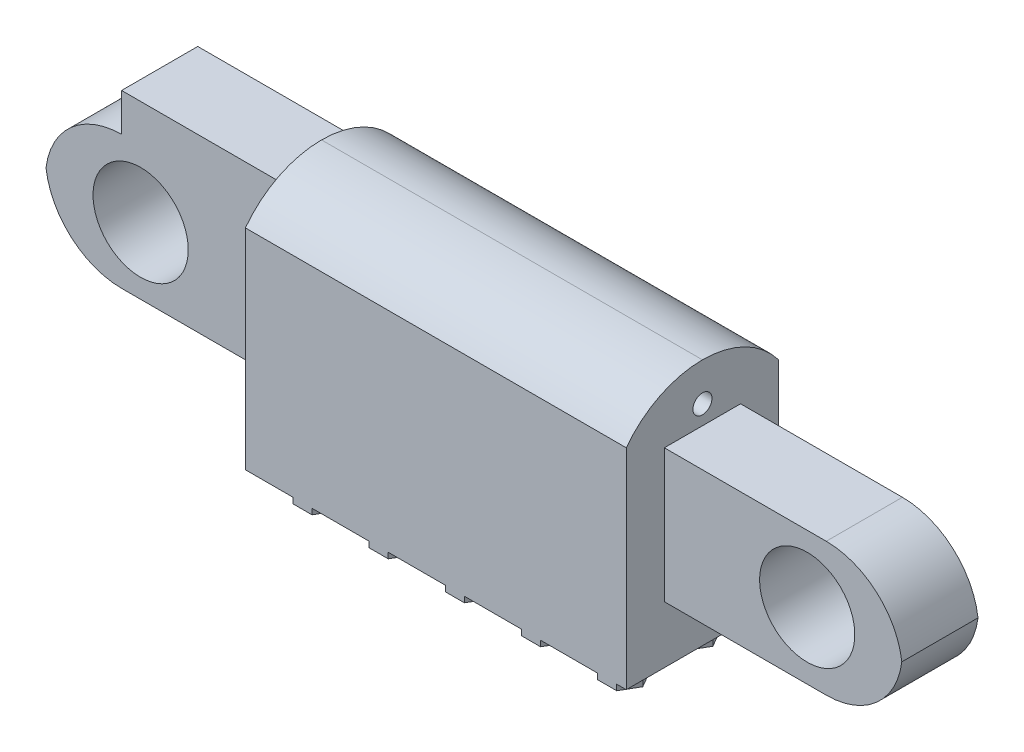
SolidWorks part; units mm, degrees
material "PLA"
ref_plane "Front" through (0, 0, 0) normal (0, 0, 1) x (1, 0, 0)
ref_plane "Top" through (0, 0, 0) normal (0, 1, 0) x (1, 0, 0)
ref_plane "Right" through (0, 0, 0) normal (1, 0, 0) x (0, 0, -1)
sketch "Sketch1" plane through (0, 0, 0) normal (0, 0, 1) x (1, 0, 0)
  line L1 (-6.35, 4.445) -> (9.525, 4.445)
  line L2 (-6.35, 4.445) -> (-6.35, -4.445)
  line L3 (-6.35, -4.445) -> (9.525, -4.445)
  line L4 (9.525, 4.445) -> (9.525, -4.445)
  circle A0 centre (0, 0) radius 3.175
  dimension "D1" = 6.35
  dimension "D2" = 6.35
  dimension "D3" = 4.445
  dimension "D4" = 4.445
  dimension "D5" = 15.875
extrude "Boss-Extrude1" add sketch "Sketch1" along normal blind 5.08
fillet "Fillet1" radius 5.08 2 edges at (-6.35, -4.445, 2.54) (-6.35, 4.445, 2.54)
sketch "Sketch2" plane through (9.525, 0, 0) normal (1, 0, 0) x (0, 0, -1)
  line L0 (-8.89, -8.255) -> (3.81, -8.255)
  line L1 (3.81, -8.255) -> (3.81, 8.255)
  line L2 (3.81, 8.255) -> (-8.89, 8.255)
  line L3 (-8.89, 8.255) -> (-8.89, -8.255)
  line L4 (0, -4.445) -> (0, 4.445)
  line L5 (0, 4.445) -> (-5.08, 4.445)
  line L6 (-5.08, 4.445) -> (-5.08, -4.445)
  line L7 (-5.08, -4.445) -> (0, -4.445)
  line L8 (0, -4.445) -> (0, 4.445)
  line L9 (0, 4.445) -> (-5.08, 4.445)
  line L10 (-5.08, 4.445) -> (-5.08, -4.445)
  line L11 (-5.08, -4.445) -> (0, -4.445)
  line M5 (0, -4.445) -> (0, 4.445)
  line M6 (0, 4.445) -> (-5.08, 4.445)
  line M7 (-5.08, 4.445) -> (-5.08, -4.445)
  line M8 (-5.08, -4.445) -> (0, -4.445)
  dimension "D1" = 0
  dimension "D2" = 3.81
extrude "Boss-Extrude2" add sketch "Sketch2" along normal blind 25.4 separate body contours L2 L3 L0 L1 M5 M8 M7 M6 | M8 M5 M6 M7 region at (9.525, 0, 8.6817) region at (9.525, 0, 2.54)
ref_plane "Plane1" through (22.225, 0, 0) normal (-1, 0, 0) x (0, 0, 1)
mirror "Mirror7" about plane through (22.225, 0, 0) normal (-1, 0, 0) of bodies 101
fillet "Fillet3" radius 6.35 2 edges at (22.225, 8.255, -3.81) (22.225, 8.255, 8.89)
sketch "Sketch3" plane through (0, 4.445, 0) normal (0, 1, 0) x (1, 0, 0)
  line L4 (9.525, 0) -> (-1.27, 0)
  line L5 (-1.27, 0) -> (-1.27, -5.08)
  line L6 (-1.27, -5.08) -> (9.525, -5.08)
  line L7 (9.525, -5.08) -> (9.525, 0)
  line L12 (9.525, 0) -> (-1.27, 0)
  line L13 (-1.27, 0) -> (-1.27, -5.08)
  line L14 (-1.27, -5.08) -> (9.525, -5.08)
  line L15 (9.525, -5.08) -> (9.525, 0)
  dimension "D1" = 0
extrude "Boss-Extrude3" add sketch "Sketch3" along normal blind 2.54
sketch "Sketch4" plane through (-1.27, 0, 0) normal (-1, 0, 0) x (0, 0, 1)
  line L8 (5.08, 6.985) -> (5.08, 4.445) construction
  line L9 (0, 4.445) -> (5.08, 4.445) construction
  circle A0 centre (2.54, 5.715) radius 0.635
  dimension "D1" = 1.27
  dimension "D2" = 1.27
  dimension "D3" = 2.54
extrude "Cut-Extrude1" cut sketch "Sketch4" against normal through all
fillet "Fillet6" radius 1.27 2 edges at (22.225, -8.255, -3.81) (22.225, -8.255, 8.89)
sketch "Sketch5" plane through (0, -8.255, 0) normal (0, -1, 0) x (1, 0, 0)
  line L0 (34.925, 1.905) -> (34.925, 3.175) construction
  line L1 (34.925, 7.62) -> (9.525, 7.62)
  line L2 (34.925, 7.62) -> (34.925, -2.54)
  line L3 (34.925, -2.54) -> (9.525, -2.54)
  line L4 (9.525, 7.62) -> (9.525, -2.54)
  line L5 (33.02, 5.4203) -> (34.29, 5.4203)
  line L6 (34.29, 5.4203) -> (34.925, 6.5201)
  line L7 (34.925, 6.5201) -> (34.29, 7.62)
  line L8 (34.29, 7.62) -> (33.02, 7.62)
  line L9 (33.02, 7.62) -> (32.385, 6.5201)
  line L10 (32.385, 6.5201) -> (33.02, 5.4203)
  line L11 (30.48, 5.4203) -> (31.75, 5.4203)
  line L12 (31.75, 5.4203) -> (32.385, 6.5201)
  line L13 (32.385, 6.5201) -> (31.75, 7.62)
  line L14 (31.75, 7.62) -> (30.48, 7.62)
  line L15 (30.48, 7.62) -> (29.845, 6.5201)
  line L16 (29.845, 6.5201) -> (30.48, 5.4203)
  line L17 (27.94, 5.4203) -> (29.21, 5.4203)
  line L18 (29.21, 5.4203) -> (29.845, 6.5201)
  line L19 (29.845, 6.5201) -> (29.21, 7.62)
  line L20 (29.21, 7.62) -> (27.94, 7.62)
  line L21 (27.94, 7.62) -> (27.305, 6.5201)
  line L22 (27.305, 6.5201) -> (27.94, 5.4203)
  line L23 (25.4, 5.4203) -> (26.67, 5.4203)
  line L24 (26.67, 5.4203) -> (27.305, 6.5201)
  line L25 (27.305, 6.5201) -> (26.67, 7.62)
  line L26 (26.67, 7.62) -> (25.4, 7.62)
  line L27 (25.4, 7.62) -> (24.765, 6.5201)
  line L28 (24.765, 6.5201) -> (25.4, 5.4203)
  line L29 (22.86, 5.4203) -> (24.13, 5.4203)
  line L30 (24.13, 5.4203) -> (24.765, 6.5201)
  line L31 (24.765, 6.5201) -> (24.13, 7.62)
  line L32 (24.13, 7.62) -> (22.86, 7.62)
  line L33 (22.86, 7.62) -> (22.225, 6.5201)
  line L34 (22.225, 6.5201) -> (22.86, 5.4203)
  line L35 (20.32, 5.4203) -> (21.59, 5.4203)
  line L36 (21.59, 5.4203) -> (22.225, 6.5201)
  line L37 (22.225, 6.5201) -> (21.59, 7.62)
  line L38 (21.59, 7.62) -> (20.32, 7.62)
  line L39 (20.32, 7.62) -> (19.685, 6.5201)
  line L40 (19.685, 6.5201) -> (20.32, 5.4203)
  line L41 (17.78, 5.4203) -> (19.05, 5.4203)
  line L42 (19.05, 5.4203) -> (19.685, 6.5201)
  line L43 (19.685, 6.5201) -> (19.05, 7.62)
  line L44 (19.05, 7.62) -> (17.78, 7.62)
  line L45 (17.78, 7.62) -> (17.145, 6.5201)
  line L46 (17.145, 6.5201) -> (17.78, 5.4203)
  line L47 (15.24, 5.4203) -> (16.51, 5.4203)
  line L48 (16.51, 5.4203) -> (17.145, 6.5201)
  line L49 (17.145, 6.5201) -> (16.51, 7.62)
  line L50 (16.51, 7.62) -> (15.24, 7.62)
  line L51 (15.24, 7.62) -> (14.605, 6.5201)
  line L52 (14.605, 6.5201) -> (15.24, 5.4203)
  line L53 (12.7, 5.4203) -> (13.97, 5.4203)
  line L54 (13.97, 5.4203) -> (14.605, 6.5201)
  line L55 (14.605, 6.5201) -> (13.97, 7.62)
  line L56 (13.97, 7.62) -> (12.7, 7.62)
  line L57 (12.7, 7.62) -> (12.065, 6.5201)
  line L58 (12.065, 6.5201) -> (12.7, 5.4203)
  line L59 (10.16, 5.4203) -> (11.43, 5.4203)
  line L60 (11.43, 5.4203) -> (12.065, 6.5201)
  line L61 (12.065, 6.5201) -> (11.43, 7.62)
  line L62 (11.43, 7.62) -> (10.16, 7.62)
  line L63 (10.16, 7.62) -> (9.525, 6.5201)
  line L64 (9.525, 6.5201) -> (10.16, 5.4203)
  line L65 (30.48, 3.0835) -> (31.75, 3.0835)
  line L66 (31.75, 3.0835) -> (32.385, 4.1833)
  line L67 (32.385, 4.1833) -> (31.75, 5.2832)
  line L68 (31.75, 5.2832) -> (30.48, 5.2832)
  line L69 (30.48, 5.2832) -> (29.845, 4.1833)
  line L70 (29.845, 4.1833) -> (30.48, 3.0835)
  line L71 (27.94, 3.0835) -> (29.21, 3.0835)
  line L72 (29.21, 3.0835) -> (29.845, 4.1833)
  line L73 (29.845, 4.1833) -> (29.21, 5.2832)
  line L74 (29.21, 5.2832) -> (27.94, 5.2832)
  line L75 (27.94, 5.2832) -> (27.305, 4.1833)
  line L76 (27.305, 4.1833) -> (27.94, 3.0835)
  line L77 (25.4, 3.0835) -> (26.67, 3.0835)
  line L78 (26.67, 3.0835) -> (27.305, 4.1833)
  line L79 (27.305, 4.1833) -> (26.67, 5.2832)
  line L80 (26.67, 5.2832) -> (25.4, 5.2832)
  line L81 (25.4, 5.2832) -> (24.765, 4.1833)
  line L82 (24.765, 4.1833) -> (25.4, 3.0835)
  line L83 (22.86, 3.0835) -> (24.13, 3.0835)
  line L84 (24.13, 3.0835) -> (24.765, 4.1833)
  line L85 (24.765, 4.1833) -> (24.13, 5.2832)
  line L86 (24.13, 5.2832) -> (22.86, 5.2832)
  line L87 (22.86, 5.2832) -> (22.225, 4.1833)
  line L88 (22.225, 4.1833) -> (22.86, 3.0835)
  line L89 (20.32, 3.0835) -> (21.59, 3.0835)
  line L90 (21.59, 3.0835) -> (22.225, 4.1833)
  line L91 (22.225, 4.1833) -> (21.59, 5.2832)
  line L92 (21.59, 5.2832) -> (20.32, 5.2832)
  line L93 (20.32, 5.2832) -> (19.685, 4.1833)
  line L94 (19.685, 4.1833) -> (20.32, 3.0835)
  line L95 (17.78, 3.0835) -> (19.05, 3.0835)
  line L96 (19.05, 3.0835) -> (19.685, 4.1833)
  line L97 (19.685, 4.1833) -> (19.05, 5.2832)
  line L98 (19.05, 5.2832) -> (17.78, 5.2832)
  line L99 (17.78, 5.2832) -> (17.145, 4.1833)
  line L100 (17.145, 4.1833) -> (17.78, 3.0835)
  line L101 (15.24, 3.0835) -> (16.51, 3.0835)
  line L102 (16.51, 3.0835) -> (17.145, 4.1833)
  line L103 (17.145, 4.1833) -> (16.51, 5.2832)
  line L104 (16.51, 5.2832) -> (15.24, 5.2832)
  line L105 (15.24, 5.2832) -> (14.605, 4.1833)
  line L106 (14.605, 4.1833) -> (15.24, 3.0835)
  line L107 (12.7, 3.0835) -> (13.97, 3.0835)
  line L108 (13.97, 3.0835) -> (14.605, 4.1833)
  line L109 (14.605, 4.1833) -> (13.97, 5.2832)
  line L110 (13.97, 5.2832) -> (12.7, 5.2832)
  line L111 (12.7, 5.2832) -> (12.065, 4.1833)
  line L112 (12.065, 4.1833) -> (12.7, 3.0835)
  line L113 (10.16, 3.0835) -> (11.43, 3.0835)
  line L114 (11.43, 3.0835) -> (12.065, 4.1833)
  line L115 (12.065, 4.1833) -> (11.43, 5.2832)
  line L116 (11.43, 5.2832) -> (10.16, 5.2832)
  line L117 (10.16, 5.2832) -> (9.525, 4.1833)
  line L118 (9.525, 4.1833) -> (10.16, 3.0835)
  line L119 (30.48, 0.7467) -> (31.75, 0.7467)
  line L120 (31.75, 0.7467) -> (32.385, 1.8465)
  line L121 (32.385, 1.8465) -> (31.75, 2.9464)
  line L122 (31.75, 2.9464) -> (30.48, 2.9464)
  line L123 (30.48, 2.9464) -> (29.845, 1.8465)
  line L124 (29.845, 1.8465) -> (30.48, 0.7467)
  line L125 (27.94, 0.7467) -> (29.21, 0.7467)
  line L126 (29.21, 0.7467) -> (29.845, 1.8465)
  line L127 (29.845, 1.8465) -> (29.21, 2.9464)
  line L128 (29.21, 2.9464) -> (27.94, 2.9464)
  line L129 (27.94, 2.9464) -> (27.305, 1.8465)
  line L130 (27.305, 1.8465) -> (27.94, 0.7467)
  line L131 (25.4, 0.7467) -> (26.67, 0.7467)
  line L132 (26.67, 0.7467) -> (27.305, 1.8465)
  line L133 (27.305, 1.8465) -> (26.67, 2.9464)
  line L134 (26.67, 2.9464) -> (25.4, 2.9464)
  line L135 (25.4, 2.9464) -> (24.765, 1.8465)
  line L136 (24.765, 1.8465) -> (25.4, 0.7467)
  line L137 (22.86, 0.7467) -> (24.13, 0.7467)
  line L138 (24.13, 0.7467) -> (24.765, 1.8465)
  line L139 (24.765, 1.8465) -> (24.13, 2.9464)
  line L140 (24.13, 2.9464) -> (22.86, 2.9464)
  line L141 (22.86, 2.9464) -> (22.225, 1.8465)
  line L142 (22.225, 1.8465) -> (22.86, 0.7467)
  line L143 (20.32, 0.7467) -> (21.59, 0.7467)
  line L144 (21.59, 0.7467) -> (22.225, 1.8465)
  line L145 (22.225, 1.8465) -> (21.59, 2.9464)
  line L146 (21.59, 2.9464) -> (20.32, 2.9464)
  line L147 (20.32, 2.9464) -> (19.685, 1.8465)
  line L148 (19.685, 1.8465) -> (20.32, 0.7467)
  line L149 (17.78, 0.7467) -> (19.05, 0.7467)
  line L150 (19.05, 0.7467) -> (19.685, 1.8465)
  line L151 (19.685, 1.8465) -> (19.05, 2.9464)
  line L152 (19.05, 2.9464) -> (17.78, 2.9464)
  line L153 (17.78, 2.9464) -> (17.145, 1.8465)
  line L154 (17.145, 1.8465) -> (17.78, 0.7467)
  line L155 (15.24, 0.7467) -> (16.51, 0.7467)
  line L156 (16.51, 0.7467) -> (17.145, 1.8465)
  line L157 (17.145, 1.8465) -> (16.51, 2.9464)
  line L158 (16.51, 2.9464) -> (15.24, 2.9464)
  line L159 (15.24, 2.9464) -> (14.605, 1.8465)
  line L160 (14.605, 1.8465) -> (15.24, 0.7467)
  line L161 (12.7, 0.7467) -> (13.97, 0.7467)
  line L162 (13.97, 0.7467) -> (14.605, 1.8465)
  line L163 (14.605, 1.8465) -> (13.97, 2.9464)
  line L164 (13.97, 2.9464) -> (12.7, 2.9464)
  line L165 (12.7, 2.9464) -> (12.065, 1.8465)
  line L166 (12.065, 1.8465) -> (12.7, 0.7467)
  line L167 (10.16, 0.7467) -> (11.43, 0.7467)
  line L168 (11.43, 0.7467) -> (12.065, 1.8465)
  line L169 (12.065, 1.8465) -> (11.43, 2.9464)
  line L170 (11.43, 2.9464) -> (10.16, 2.9464)
  line L171 (10.16, 2.9464) -> (9.525, 1.8465)
  line L172 (9.525, 1.8465) -> (10.16, 0.7467)
  line L173 (30.48, -1.5901) -> (31.75, -1.5901)
  line L174 (31.75, -1.5901) -> (32.385, -0.4903)
  line L175 (32.385, -0.4903) -> (31.75, 0.6096)
  line L176 (31.75, 0.6096) -> (30.48, 0.6096)
  line L177 (30.48, 0.6096) -> (29.845, -0.4903)
  line L178 (29.845, -0.4903) -> (30.48, -1.5901)
  line L179 (27.94, -1.5901) -> (29.21, -1.5901)
  line L180 (29.21, -1.5901) -> (29.845, -0.4903)
  line L181 (29.845, -0.4903) -> (29.21, 0.6096)
  line L182 (29.21, 0.6096) -> (27.94, 0.6096)
  line L183 (27.94, 0.6096) -> (27.305, -0.4903)
  line L184 (27.305, -0.4903) -> (27.94, -1.5901)
  line L185 (25.4, -1.5901) -> (26.67, -1.5901)
  line L186 (26.67, -1.5901) -> (27.305, -0.4903)
  line L187 (27.305, -0.4903) -> (26.67, 0.6096)
  line L188 (26.67, 0.6096) -> (25.4, 0.6096)
  line L189 (25.4, 0.6096) -> (24.765, -0.4903)
  line L190 (24.765, -0.4903) -> (25.4, -1.5901)
  line L191 (22.86, -1.5901) -> (24.13, -1.5901)
  line L192 (24.13, -1.5901) -> (24.765, -0.4903)
  line L193 (24.765, -0.4903) -> (24.13, 0.6096)
  line L194 (24.13, 0.6096) -> (22.86, 0.6096)
  line L195 (22.86, 0.6096) -> (22.225, -0.4903)
  line L196 (22.225, -0.4903) -> (22.86, -1.5901)
  line L197 (20.32, -1.5901) -> (21.59, -1.5901)
  line L198 (21.59, -1.5901) -> (22.225, -0.4903)
  line L199 (22.225, -0.4903) -> (21.59, 0.6096)
  line L200 (21.59, 0.6096) -> (20.32, 0.6096)
  line L201 (20.32, 0.6096) -> (19.685, -0.4903)
  line L202 (19.685, -0.4903) -> (20.32, -1.5901)
  line L203 (17.78, -1.5901) -> (19.05, -1.5901)
  line L204 (19.05, -1.5901) -> (19.685, -0.4903)
  line L205 (19.685, -0.4903) -> (19.05, 0.6096)
  line L206 (19.05, 0.6096) -> (17.78, 0.6096)
  line L207 (17.78, 0.6096) -> (17.145, -0.4903)
  line L208 (17.145, -0.4903) -> (17.78, -1.5901)
  line L209 (15.24, -1.5901) -> (16.51, -1.5901)
  line L210 (16.51, -1.5901) -> (17.145, -0.4903)
  line L211 (17.145, -0.4903) -> (16.51, 0.6096)
  line L212 (16.51, 0.6096) -> (15.24, 0.6096)
  line L213 (15.24, 0.6096) -> (14.605, -0.4903)
  line L214 (14.605, -0.4903) -> (15.24, -1.5901)
  line L215 (12.7, -1.5901) -> (13.97, -1.5901)
  line L216 (13.97, -1.5901) -> (14.605, -0.4903)
  line L217 (14.605, -0.4903) -> (13.97, 0.6096)
  line L218 (13.97, 0.6096) -> (12.7, 0.6096)
  line L219 (12.7, 0.6096) -> (12.065, -0.4903)
  line L220 (12.065, -0.4903) -> (12.7, -1.5901)
  line L221 (10.16, -1.5901) -> (11.43, -1.5901)
  line L222 (11.43, -1.5901) -> (12.065, -0.4903)
  line L223 (12.065, -0.4903) -> (11.43, 0.6096)
  line L224 (11.43, 0.6096) -> (10.16, 0.6096)
  line L225 (10.16, 0.6096) -> (9.525, -0.4903)
  line L226 (9.525, -0.4903) -> (10.16, -1.5901)
  line L227 (30.48, -3.9269) -> (31.75, -3.9269)
  line L228 (31.75, -3.9269) -> (32.385, -2.8271)
  line L229 (32.385, -2.8271) -> (31.75, -1.7272)
  line L230 (31.75, -1.7272) -> (30.48, -1.7272)
  line L231 (30.48, -1.7272) -> (29.845, -2.8271)
  line L232 (29.845, -2.8271) -> (30.48, -3.9269)
  line L233 (27.94, -3.9269) -> (29.21, -3.9269)
  line L234 (29.21, -3.9269) -> (29.845, -2.8271)
  line L235 (29.845, -2.8271) -> (29.21, -1.7272)
  line L236 (29.21, -1.7272) -> (27.94, -1.7272)
  line L237 (27.94, -1.7272) -> (27.305, -2.8271)
  line L238 (27.305, -2.8271) -> (27.94, -3.9269)
  line L239 (25.4, -3.9269) -> (26.67, -3.9269)
  line L240 (26.67, -3.9269) -> (27.305, -2.8271)
  line L241 (27.305, -2.8271) -> (26.67, -1.7272)
  line L242 (26.67, -1.7272) -> (25.4, -1.7272)
  line L243 (25.4, -1.7272) -> (24.765, -2.8271)
  line L244 (24.765, -2.8271) -> (25.4, -3.9269)
  line L245 (22.86, -3.9269) -> (24.13, -3.9269)
  line L246 (24.13, -3.9269) -> (24.765, -2.8271)
  line L247 (24.765, -2.8271) -> (24.13, -1.7272)
  line L248 (24.13, -1.7272) -> (22.86, -1.7272)
  line L249 (22.86, -1.7272) -> (22.225, -2.8271)
  line L250 (22.225, -2.8271) -> (22.86, -3.9269)
  line L251 (20.32, -3.9269) -> (21.59, -3.9269)
  line L252 (21.59, -3.9269) -> (22.225, -2.8271)
  line L253 (22.225, -2.8271) -> (21.59, -1.7272)
  line L254 (21.59, -1.7272) -> (20.32, -1.7272)
  line L255 (20.32, -1.7272) -> (19.685, -2.8271)
  line L256 (19.685, -2.8271) -> (20.32, -3.9269)
  line L257 (17.78, -3.9269) -> (19.05, -3.9269)
  line L258 (19.05, -3.9269) -> (19.685, -2.8271)
  line L259 (19.685, -2.8271) -> (19.05, -1.7272)
  line L260 (19.05, -1.7272) -> (17.78, -1.7272)
  line L261 (17.78, -1.7272) -> (17.145, -2.8271)
  line L262 (17.145, -2.8271) -> (17.78, -3.9269)
  line L263 (15.24, -3.9269) -> (16.51, -3.9269)
  line L264 (16.51, -3.9269) -> (17.145, -2.8271)
  line L265 (17.145, -2.8271) -> (16.51, -1.7272)
  line L266 (16.51, -1.7272) -> (15.24, -1.7272)
  line L267 (15.24, -1.7272) -> (14.605, -2.8271)
  line L268 (14.605, -2.8271) -> (15.24, -3.9269)
  line L269 (12.7, -3.9269) -> (13.97, -3.9269)
  line L270 (13.97, -3.9269) -> (14.605, -2.8271)
  line L271 (14.605, -2.8271) -> (13.97, -1.7272)
  line L272 (13.97, -1.7272) -> (12.7, -1.7272)
  line L273 (12.7, -1.7272) -> (12.065, -2.8271)
  line L274 (12.065, -2.8271) -> (12.7, -3.9269)
  line L275 (10.16, -3.9269) -> (11.43, -3.9269)
  line L276 (11.43, -3.9269) -> (12.065, -2.8271)
  line L277 (12.065, -2.8271) -> (11.43, -1.7272)
  line L278 (11.43, -1.7272) -> (10.16, -1.7272)
  line L279 (10.16, -1.7272) -> (9.525, -2.8271)
  line L280 (9.525, -2.8271) -> (10.16, -3.9269)
  line L281 (33.02, 3.0835) -> (34.29, 3.0835)
  line L282 (34.29, 3.0835) -> (34.925, 4.1833)
  line L283 (34.925, 4.1833) -> (34.29, 5.2832)
  line L284 (34.29, 5.2832) -> (33.02, 5.2832)
  line L285 (33.02, 5.2832) -> (32.385, 4.1833)
  line L286 (32.385, 4.1833) -> (33.02, 3.0835)
  line L287 (33.02, 0.7467) -> (34.29, 0.7467)
  line L288 (34.29, 0.7467) -> (34.925, 1.8465)
  line L289 (34.925, 1.8465) -> (34.29, 2.9464)
  line L290 (34.29, 2.9464) -> (33.02, 2.9464)
  line L291 (33.02, 2.9464) -> (32.385, 1.8465)
  line L292 (32.385, 1.8465) -> (33.02, 0.7467)
  line L293 (33.02, -1.5901) -> (34.29, -1.5901)
  line L294 (34.29, -1.5901) -> (34.925, -0.4903)
  line L295 (34.925, -0.4903) -> (34.29, 0.6096)
  line L296 (34.29, 0.6096) -> (33.02, 0.6096)
  line L297 (33.02, 0.6096) -> (32.385, -0.4903)
  line L298 (32.385, -0.4903) -> (33.02, -1.5901)
  line L299 (33.02, -3.9269) -> (34.29, -3.9269)
  line L300 (34.29, -3.9269) -> (34.925, -2.8271)
  line L301 (34.925, -2.8271) -> (34.29, -1.7272)
  line L302 (34.29, -1.7272) -> (33.02, -1.7272)
  line L303 (33.02, -1.7272) -> (32.385, -2.8271)
  line L304 (32.385, -2.8271) -> (33.02, -3.9269)
  circle A0 centre (33.655, 6.5201) radius 1.0999 construction
  dimension "D1" = 2.54
  dimension "D2" = 10
  dimension "D3" = 5
extrude "Boss-Extrude7" add sketch "Sketch5" along normal blind 0.381 contours L9 L10 L5 L6 L7 L1 | L21 L22 L17 L18 L19 L1 | L33 L34 L29 L30 L31 L1 | L45 L46 L41 L42 L43 L1 | L57 L58 L53 L54 L55 L1 | L65 L66 L67 L68 L69 L70 | L77 L78 L79 L80 L81 L82 | L89 L90 L91 L92 L93 L94 | L101 L102 L103 L104 L105 L106 | L113 L114 L115 L116 L117 L118 | L287 L288 L289 L290 L291 L292 | L125 L126 L127 L128 L129 L130 | L137 L138 L139 L140 L141 L142 | L149 L150 L151 L152 L153 L154 | L161 L162 L163 L164 L165 L166 | L173 L174 L175 L176 L177 L178 | L185 L186 L187 L188 L189 L190 | L197 L198 L199 L200 L201 L202 | L209 L210 L211 L212 L213 L214 | L221 L222 L223 L224 L225 L226 region at (33.655, -8.255, 6.5201) region at (28.575, -8.255, 6.5201) region at (23.495, -8.255, 6.5201) region at (18.415, -8.255, 6.5201) region at (13.335, -8.255, 6.5201)
sketch "Sketch6" plane through (0, 0, 8.89) normal (0, 0, 1) x (1, 0, 0)
  line L1 (8.3955, 10.7841) -> (40.791, 10.7841)
  line L2 (8.3955, 10.7841) -> (8.3955, -17.2444)
  line L3 (8.3955, -17.2444) -> (40.791, -17.2444)
  line L4 (40.791, 10.7841) -> (40.791, -17.2444)
extrude "Cut-Extrude2" cut sketch "Sketch6" against normal blind 1.27
sketch "Sketch7" plane through (0, 0, -3.81) normal (0, 0, -1) x (-1, 0, 0)
  line L1 (-38.2145, 12.6459) -> (-2.9704, 12.6459)
  line L2 (-38.2145, 12.6459) -> (-38.2145, -13.023)
  line L3 (-38.2145, -13.023) -> (-2.9704, -13.023)
  line L4 (-2.9704, 12.6459) -> (-2.9704, -13.023)
extrude "Cut-Extrude3" cut sketch "Sketch7" against normal blind 1.27
